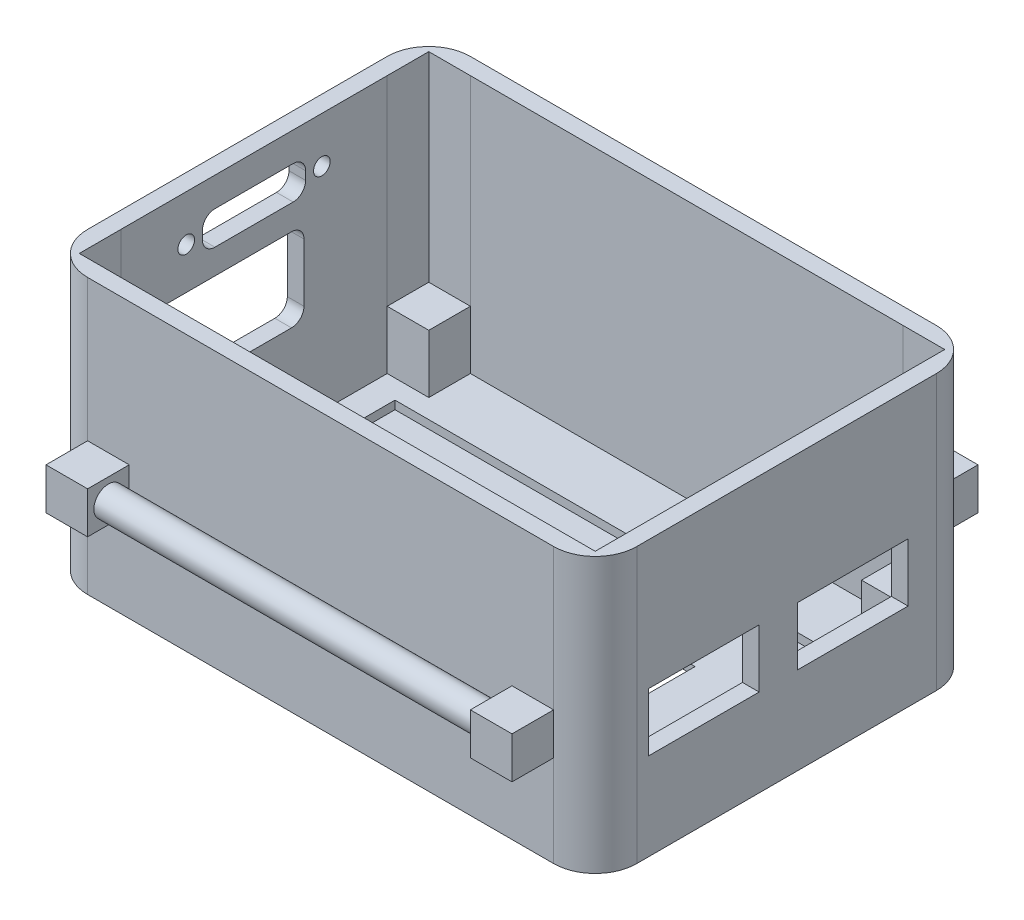
SolidWorks part; units mm, degrees
ref_plane "Front Plane" through (0, 0, 0) normal (0, 0, 1) x (1, 0, 0)
ref_plane "Top Plane" through (0, 0, 0) normal (0, 1, 0) x (1, 0, 0)
ref_plane "Right Plane" through (0, 0, 0) normal (1, 0, 0) x (0, 0, -1)
sketch "Sketch1" plane through (0, 0, 0) normal (0, 1, 0) x (1, 0, 0)
  line L0 (0, 23) -> (66, 23) construction
  line L1 (5, 0) -> (61, 0)
  line L2 (0, 5) -> (0, 41)
  line L3 (5, 46) -> (61, 46)
  line L4 (66, 5) -> (66, 41)
  line L5 (33, 46) -> (33, 0) construction
  line L6 (64, 39) -> (59, 39)
  line L7 (64, 44) -> (2, 44)
  line L8 (64, 44) -> (64, 2)
  line L9 (64, 2) -> (2, 2)
  line L10 (2, 44) -> (2, 2)
  line L11 (64, 44) -> (2, 2) construction
  line L12 (64, 2) -> (2, 44) construction
  line L13 (2, 44) -> (7, 44)
  line L14 (2, 44) -> (2, 39)
  line L15 (2, 39) -> (7, 39)
  line L16 (7, 44) -> (7, 39)
  line L17 (59, 44) -> (59, 39)
  line L18 (7, 2) -> (7, 7)
  line L19 (2, 7) -> (7, 7)
  line L20 (64, 7) -> (59, 7)
  line L21 (59, 2) -> (59, 7)
  line L22 (2, 39) -> (2, 44)
  line L23 (2, 7) -> (2, 2)
  line L24 (7, 2) -> (2, 2)
  line L25 (59, 44) -> (64, 44)
  line L26 (64, 39) -> (64, 44)
  line L27 (59, 2) -> (64, 2)
  line L28 (64, 7) -> (64, 2)
  line L29 (7, 44) -> (2, 44)
  line L30 (2, 39) -> (2, 44)
  arc A0 (5, 46) -> (0, 41) centre (5, 41) ccw
  arc A1 (0, 5) -> (5, 0) centre (5, 5) ccw
  arc A2 (61, 0) -> (66, 5) centre (61, 5) ccw
  arc A3 (66, 41) -> (61, 46) centre (61, 41) ccw
  point P9 (33, 23)
  point P16 (0, 46)
  point P19 (0, 0)
  point P22 (66, 0)
  point P25 (66, 46)
  point P38 (42, 22)
  dimension "D5" = 5
  dimension "D1" = 66
  dimension "D2" = 46
  dimension "D3" = 62
  dimension "D4" = 42
  dimension "D6" = 5
  dimension "D7" = 5
extrude "Boss-Extrude4" add sketch "Sketch1" along normal blind 33 contours L9 L21 L20 L8 L6 L17 L7 L16 L15 L10 L19 L18 | A1 L1 A2 L4 A3 L3 A0 L2 | L8 L7 L10 L9 region at (33, 0, -23)
extrude "Boss-Extrude6" add sketch "Sketch1<4>" along normal blind 2 contours L10 L9 L8 L7
sketch "Sketch1<4>" plane through (0, 0, 0) normal (0, 1, 0) x (1, 0, 0) same geometry as "Sketch1"
extrude "Boss-Extrude7" add sketch "Sketch1<7>" along normal blind 9 contours L16 L7 L10 L15 | L21 L9 L8 L20 | L26 L6 L17 L25 | L24 L18 L19 L23 region at (61.5, 0, -4.5) region at (4.5, 0, -41.5)
sketch "Sketch1<7>" plane through (0, 0, 0) normal (0, 1, 0) x (1, 0, 0) same geometry as "Sketch1"
sketch "Sketch5" plane through (0, 2, 0) normal (0, 1, 0) x (1, 0, 0)
  line L0 (33, 44) -> (33, 2) construction
  line L1 (59, 44) -> (7, 44) construction
  line L2 (59, 2) -> (7, 2) construction
  line L3 (33, 23) -> (64, 23) construction
  line L4 (64, 39) -> (64, 7) construction
  line L5 (64, 39) -> (64, 7) construction
  line L6 (50, 28) -> (40, 28)
  line L7 (50, 28) -> (50, 18)
  line L8 (50, 18) -> (40, 18)
  line L9 (40, 28) -> (40, 18)
  line L10 (50, 28) -> (40, 18) construction
  line L11 (50, 18) -> (40, 28) construction
  point P10 (45, 23)
  dimension "D1" = 10
  dimension "D2" = 10
  dimension "D3" = 14
extrude "Cut-Extrude1" cut sketch "Sketch5" against normal through all contours L6 L9 L8 L7 | L7 L6 L9 L8 region at (45, 2, -23)
sketch "Sketch7" plane through (66, 0, 0) normal (1, 0, 0) x (0, 0, -1)
  line L0 (0, 16.5) -> (46, 16.5) construction
  line L3 (0, 33) -> (0, 0) construction
  line L4 (46, 33) -> (46, 0) construction
  line L5 (23, 33) -> (23, 0) construction
  line L6 (5, 33) -> (41, 33) construction
  line L7 (5, 0) -> (41, 0) construction
  line L9 (0, 10.5) -> (46, 10.5) construction
  line L12 (19.7, 10.5) -> (6.4, 10.5)
  line L13 (19.7, 10.5) -> (19.7, 17.5)
  line L14 (19.7, 17.5) -> (6.4, 17.5)
  line L15 (6.4, 10.5) -> (6.4, 17.5)
  line L16 (24.3, 10.5) -> (37.6, 10.5)
  line L17 (24.3, 10.5) -> (24.3, 17.5)
  line L18 (24.3, 17.5) -> (37.6, 17.5)
  line L19 (37.6, 10.5) -> (37.6, 17.5)
  dimension "D1" = 4.6
  dimension "D2" = 10.5
  dimension "D3" = 7
  dimension "D4" = 13.3
  dimension "D5" = 10.5
  dimension "D6" = 7
  dimension "D7" = 13.3
extrude "Cut-Extrude3" cut sketch "Sketch7" against normal blind 10 contours L16 L19 L18 L17 | L13 L12 L15 L14 region at (66, 14, -30.95)
sketch "Sketch8" plane through (0, 0, 0) normal (0, 0, 1) x (1, 0, 0)
  line L0 (33, 33) -> (33, 0) construction
  line L1 (5, 33) -> (61, 33) construction
  line L2 (5, 0) -> (61, 0) construction
  line L4 (5, 11) -> (61, 11) construction
  line L5 (5, 33) -> (5, 0) construction
  line L6 (61, 33) -> (61, 0) construction
  line L7 (61, 16) -> (56, 16)
  line L8 (5, 11) -> (10, 11)
  line L9 (5, 11) -> (5, 16)
  line L10 (5, 16) -> (10, 16)
  line L11 (10, 11) -> (10, 16)
  line L12 (56, 11) -> (56, 16)
  line L13 (61, 11) -> (56, 11)
  line L14 (61, 11) -> (61, 16)
  line M12 (61, 0) -> (61, 33)
  dimension "D1" = 11
  dimension "D2" = 5
  dimension "D3" = 5
extrude "Boss-Extrude11" add sketch "Sketch8" along normal blind 5 contours L13 L7 L12 M12 | L9 L8 L11 L10 region at (58.5, 13.5, 0)
sketch "Sketch9" plane through (61, 0, 0) normal (1, 0, 0) x (0, 0, -1)
  line L0 (-5, 16) -> (0, 11) construction
  line L1 (0, 11) -> (-5, 11) construction
  line L2 (-5, 11) -> (0, 16) construction
  circle A0 centre (-2.5, 13.5) radius 1.75
  dimension "D1" = 3.5
extrude "Boss-Extrude13" add sketch "Sketch9" against normal blind 55 separate body
sketch "Sketch11" plane through (0, 0, -46) normal (0, 0, -1) x (-1, 0, 0)
  line L0 (-33, 0) -> (-33, 33) construction
  line L1 (-5, 0) -> (-61, 0) construction
  line L2 (-5, 33) -> (-61, 33) construction
  line L6 (-61, 11) -> (-5, 11) construction
  line L7 (-61, 33) -> (-61, 0) construction
  line L8 (-5, 33) -> (-5, 0) construction
  line L9 (-5, 16) -> (-10, 16)
  line L10 (-61, 11) -> (-56, 11)
  line L11 (-61, 11) -> (-61, 16)
  line L12 (-61, 16) -> (-56, 16)
  line L13 (-56, 11) -> (-56, 16)
  line L14 (-10, 11) -> (-10, 16)
  line L15 (-5, 11) -> (-10, 11)
  line L16 (-5, 11) -> (-5, 16)
  dimension "D1" = 11
  dimension "D2" = 5
  dimension "D3" = 5
extrude "Boss-Extrude14" add sketch "Sketch11" along normal blind 5 contours L11 L10 L13 L12 | L9 L14 L15 L16
sketch "Sketch12" plane through (61, 0, 0) normal (1, 0, 0) x (0, 0, -1)
  line L0 (-5, 16) -> (0, 11) construction
  line L3 (0, 11) -> (-5, 11) construction
  line L4 (-5, 11) -> (0, 16) construction
  line L5 (46, 16) -> (51, 11) construction
  line L6 (46, 11) -> (51, 16) construction
  circle A0 centre (48.5, 13.5) radius 1.75
  dimension "D1" = 3.5
extrude "Boss-Extrude16" add sketch "Sketch12" against normal blind 55 contours A0 | A0 region at (61, 13.5, -48.5)
sketch "Sketch13" plane through (0, 0, 0) normal (-1, 0, 0) x (0, 0, 1)
  line L0 (-23, 33) -> (-23, 0) construction
  line L1 (-5, 33) -> (-41, 33) construction
  line L2 (-5, 0) -> (-41, 0) construction
  line L3 (-41, 16.5) -> (-5, 16.5) construction
  line L4 (-41, 33) -> (-41, 0) construction
  line L5 (-5, 33) -> (-5, 0) construction
  line L6 (-16.8, 27.5) -> (-29.2, 27.5)
  line L7 (0, 11) -> (-46, 11) construction
  line L8 (-27.7, 29.5) -> (-18.3, 29.5)
  line L9 (-29.2, 28) -> (-29.2, 27)
  line L10 (-27.7, 25.5) -> (-18.3, 25.5)
  line L11 (-16.8, 28) -> (-16.8, 27)
  line L12 (-29.2, 29.5) -> (-16.8, 25.5) construction
  line L13 (-29.2, 25.5) -> (-16.8, 29.5) construction
  line L14 (-23, 11) -> (-44, 11)
  line L16 (-23, 17.5) -> (-44, 17.5) construction
  line L17 (-44, 17.5) -> (-20, 17.5) construction
  line L19 (-27.5, 22.5) -> (-12.5, 22.5)
  line L20 (-29, 21) -> (-29, 14)
  line L21 (-27.5, 12.5) -> (-12.5, 12.5)
  line L22 (-11, 21) -> (-11, 14)
  line L23 (-29, 22.5) -> (-11, 12.5) construction
  line L24 (-29, 12.5) -> (-11, 22.5) construction
  line L25 (-29, 23.75) -> (-11, 23.75)
  line L26 (-30.5, 22.25) -> (-30.5, 12.75)
  line L27 (-29, 11.25) -> (-11, 11.25)
  line L28 (-9.5, 22.25) -> (-9.5, 12.75)
  line L29 (-30.5, 23.75) -> (-9.5, 11.25) construction
  line L30 (-30.5, 11.25) -> (-9.5, 23.75) construction
  circle A4 centre (-31.15, 27.5) radius 1
  circle A5 centre (-14.85, 27.5) radius 1
  arc A6 (-27.7, 29.5) -> (-29.2, 28) centre (-27.7, 28) ccw
  arc A7 (-27.7, 25.5) -> (-29.2, 27) centre (-27.7, 27) cw
  arc A8 (-18.3, 25.5) -> (-16.8, 27) centre (-18.3, 27) ccw
  arc A9 (-16.8, 28) -> (-18.3, 29.5) centre (-18.3, 28) ccw
  arc A10 (-27.5, 12.5) -> (-29, 14) centre (-27.5, 14) cw
  arc A11 (-12.5, 12.5) -> (-11, 14) centre (-12.5, 14) ccw
  arc A12 (-11, 21) -> (-12.5, 22.5) centre (-12.5, 21) ccw
  arc A13 (-27.5, 22.5) -> (-29, 21) centre (-27.5, 21) ccw
  arc A14 (-11, 23.75) -> (-9.5, 22.25) centre (-11, 22.25) cw
  arc A15 (-11, 11.25) -> (-9.5, 12.75) centre (-11, 12.75) ccw
  arc A16 (-29, 11.25) -> (-30.5, 12.75) centre (-29, 12.75) cw
  arc A17 (-30.5, 22.25) -> (-29, 23.75) centre (-29, 22.25) cw
  dimension "D4" = 46
  dimension "D6" = 16.3
  dimension "D7" = 1.5
  dimension "D13" = 1.5
  dimension "D16" = 1.5
  dimension "D2" = 12.4
  dimension "D3" = 4
  dimension "D5" = 27.5
  dimension "D8" = 21
  dimension "D9" = 17.5
  dimension "D10" = 24
  dimension "D11" = 18
  dimension "D12" = 10
  dimension "D14" = 12.5
  dimension "D15" = 21
  dimension "D17" = 27.5
extrude "Cut-Extrude10" cut sketch "Sketch13" against normal blind 10 contours L9 L10 L11 L8 | A9 L8 A6 L9 A7 L10 A8 L11 region at (0, 26.5269, -23)
extrude "Cut-Extrude11" cut sketch "Sketch13<4>" against normal blind 10 contours A4 | A5
sketch "Sketch13<4>" plane through (0, 0, 0) normal (-1, 0, 0) x (0, 0, 1) same geometry as "Sketch13"
extrude "Cut-Extrude12" cut sketch "Sketch13<5>" against normal blind 10 contours L19 A12 L22 A11 L21 A10 L20 A13
sketch "Sketch13<5>" plane through (0, 0, 0) normal (-1, 0, 0) x (0, 0, 1) same geometry as "Sketch13"
sketch "Sketch14" plane through (0, 2, 0) normal (0, 1, 0) x (1, 0, 0)
  line L3 (33, 44) -> (33, 2) construction
  line L8 (5.238, 36.7015) -> (60.762, 36.7015)
  line L9 (5.238, 36.7015) -> (5.238, 9.2985)
  line L10 (59, 44) -> (7, 44) construction
  line L11 (59, 2) -> (7, 2) construction
  line L12 (5.238, 9.2985) -> (60.762, 9.2985)
  line L13 (60.762, 36.7015) -> (60.762, 9.2985)
  line L14 (5.238, 36.7015) -> (60.762, 9.2985) construction
  line L15 (5.238, 9.2985) -> (60.762, 36.7015) construction
  point P0 (33, 23)
extrude "Cut-Extrude13" cut sketch "Sketch14" against normal blind 1
